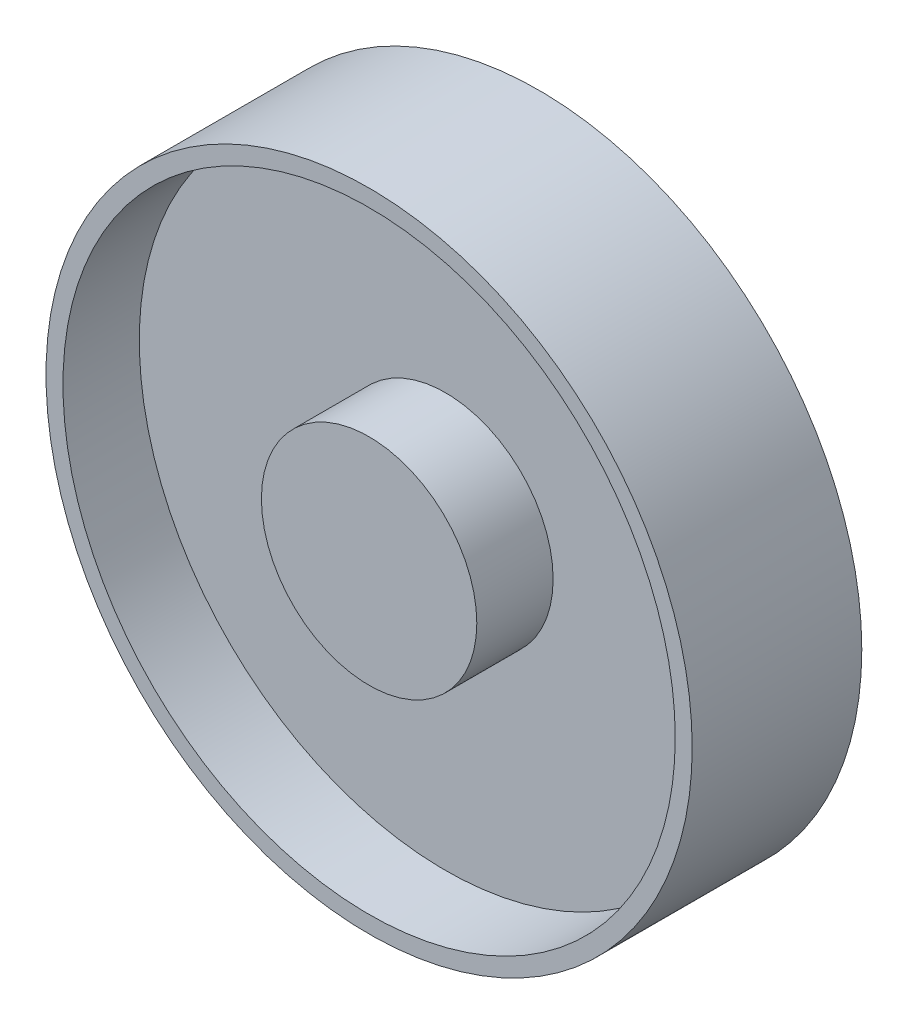
SolidWorks part; units mm, degrees
material "Silicon Rubber"
ref_plane "Front Plane" through (0, 0, 0) normal (0, 0, 1) x (1, 0, 0)
ref_plane "Top Plane" through (0, 0, 0) normal (0, 1, 0) x (1, 0, 0)
ref_plane "Right Plane" through (0, 0, 0) normal (1, 0, 0) x (0, 0, -1)
sketch "Sketch1" plane through (0, 0, 0) normal (0, 0, 1) x (1, 0, 0)
  circle A0 centre (0, 0) radius 6.35
  circle A1 centre (0, 0) radius 18.05
  circle A2 centre (0, 0) radius 19.05
  dimension "D1" = 12.7
  dimension "D2" = 12.7
  dimension "D3" = 1
extrude "Boss-Extrude1" add sketch "Sketch1" along normal mid plane 1 contours A1 A0 region at (-17.5395, 0, 0)
extrude "Boss-Extrude2" add sketch "Sketch1<3>" along normal mid plane 10 contours A0 | A2 A1 region at (0, 0, 0) region at (-18.5112, 0, 0)
sketch "Sketch1<3>" plane through (0, 0, 0) normal (0, 0, 1) x (1, 0, 0) same geometry as "Sketch1"
